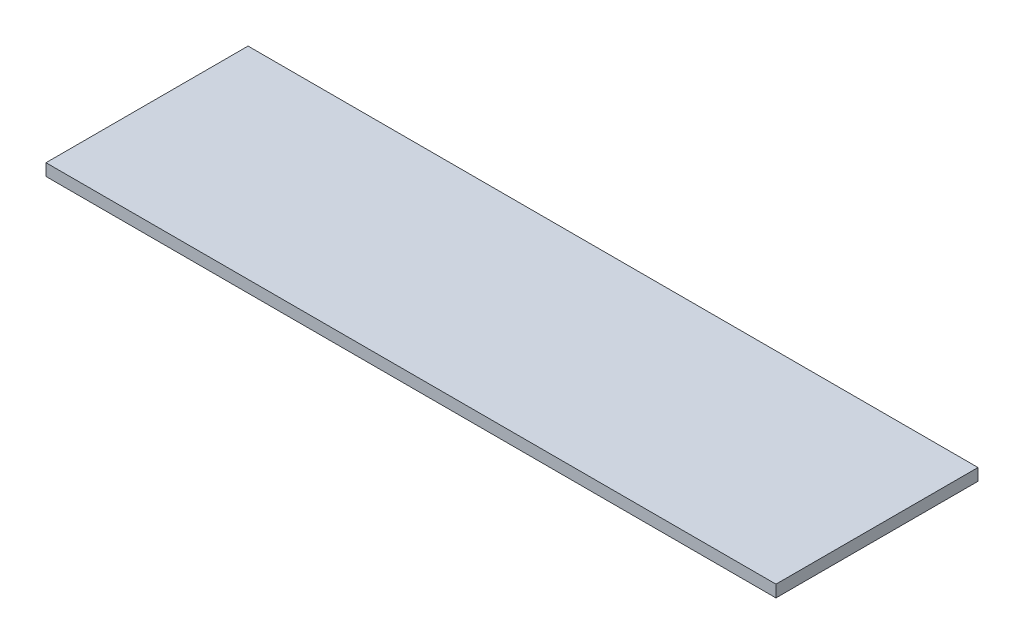
SolidWorks part; units mm, degrees
material "Cedar"
ref_plane "Front Plane" through (0, 0, 0) normal (0, 0, 1) x (1, 0, 0)
ref_plane "Top Plane" through (0, 0, 0) normal (0, 1, 0) x (1, 0, 0)
ref_plane "Right Plane" through (0, 0, 0) normal (1, 0, 0) x (0, 0, -1)
sketch "Sketch1" plane through (0, 0, 0) normal (0, 1, 0) x (1, 0, 0)
  line L1 (-533.4, -147.6375) -> (533.4, -147.6375)
  line L2 (-533.4, -147.6375) -> (-533.4, 147.6375)
  line L3 (-533.4, 147.6375) -> (533.4, 147.6375)
  line L4 (533.4, -147.6375) -> (533.4, 147.6375)
  line L5 (-533.4, -147.6375) -> (533.4, 147.6375) construction
  line L6 (-533.4, 147.6375) -> (533.4, -147.6375) construction
  point P0 (0, 0)
  dimension "D1" = 1066.8
  dimension "D2" = 295.275
extrude "Boss-Extrude1" add sketch "Sketch1" along normal blind 17.4752
